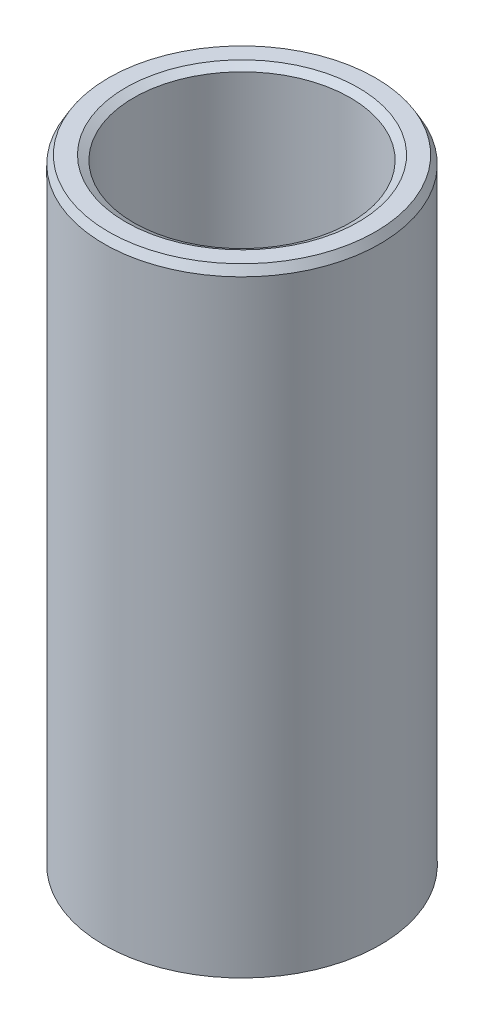
SolidWorks part; units mm, degrees
ref_plane "Front Plane" through (0, 0, 0) normal (0, 0, 1) x (1, 0, 0)
ref_plane "Top Plane" through (0, 0, 0) normal (0, 1, 0) x (1, 0, 0)
ref_plane "Right Plane" through (0, 0, 0) normal (1, 0, 0) x (0, 0, -1)
sketch "Sketch1" plane through (0, 0, 0) normal (0, 1, 0) x (1, 0, 0)
  circle A0 centre (0, 0) radius 37.5
  dimension "SLEEVE_OD" = 75
extrude "Boss-Extrude1" add sketch "Sketch1" along normal blind 168.3579
sketch "Sketch2" plane through (0, 0, 0) normal (0, 1, 0) x (1, 0, 0)
  circle A0 centre (0, 0) radius 29.4083
  dimension "BORE_D" = 58.8166
extrude "Cut-Extrude1" cut sketch "Sketch2" along normal through all
chamfer "Chamfer1" distance 2.193 angle 30 4 edges at (0, 168.3579, 29.4083) (0, 0, 29.4083) (0, 0, 37.5) (0, 168.3579, 37.5) first distance on face at (0, 168.3579, 29.4083) first distance on face at (0, 0, 29.4083) first distance on face at (0, 168.3579, 37.5)
